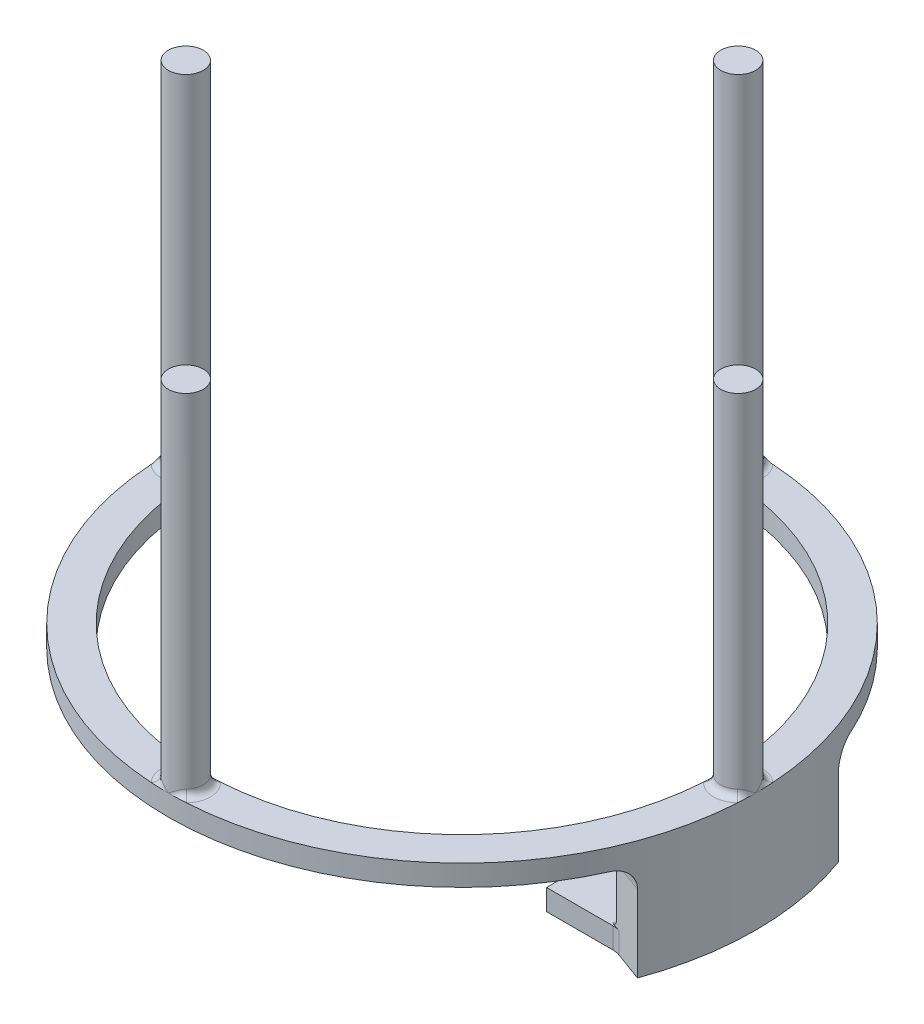
SolidWorks part; units mm, degrees
material "ABS"
ref_plane "前视基准面" through (0, 0, 0) normal (0, 0, 1) x (1, 0, 0)
ref_plane "上视基准面" through (0, 0, 0) normal (0, 1, 0) x (1, 0, 0)
ref_plane "右视基准面" through (0, 0, 0) normal (1, 0, 0) x (0, 0, -1)
other "Configuration Table"
sketch "草图1" plane through (0, 0, 0) normal (0, 1, 0) x (1, 0, 0)
  line L0 (-42, 0) -> (-37, 0)
  line L1 (0, 42) -> (0, 37)
  line L2 (0, 0) -> (0, 37) construction
  circle A0 centre (0, 0) radius 42 construction
  circle A1 centre (0, 0) radius 37 construction
  arc A2 (-37, 0) -> (0, 37) centre (0, 0) ccw
  arc A3 (-42, 0) -> (0, 42) centre (0, 0) ccw
  dimension "D1" = 84
  dimension "D2" = 74
extrude "凸台-拉伸1" add sketch "草图1" along normal blind 3
sketch "草图2" plane through (0, 3, 0) normal (0, 1, 0) x (1, 0, 0)
  line L0 (0, 42) -> (0, 37) construction
  line L1 (-37, 0) -> (-42, 0) construction
  line L2 (-39.5, 0) -> (0, 0) construction
  line L3 (0, 0) -> (0, 39.5) construction
  line L4 (0, 0) -> (39.5, 0) construction
  line L5 (0, 0) -> (0, -39.5) construction
  circle A0 centre (0, 39.5) radius 2.5
  circle A1 centre (-39.5, 0) radius 2.5
  circle A2 centre (39.5, 0) radius 2.5
  circle A3 centre (0, -39.5) radius 2.5
  point P15 (0, -44.3752)
extrude "凸台-拉伸2" add sketch "草图2" along normal blind 50 and the other way blind 3
sketch "草图3" plane through (0, 0, 0) normal (0, -1, 0) x (1, 0, 0)
  line L0 (0, 0) -> (82.8518, 0) construction
  line L1 (0, 0) -> (34.7686, 12.6547) construction
  line L2 (0, 0) -> (34.7686, -12.6547) construction
  line L3 (39.4671, 14.3648) -> (34.7686, 12.6547)
  line L4 (39.4671, -14.3648) -> (34.7686, -12.6547)
  arc A0 (0, -42) -> (-42, 0) centre (0, 0) ccw construction
  arc A1 (39.4671, -14.3648) -> (39.4671, 14.3648) centre (0, 0) ccw
  arc A2 (34.7686, -12.6547) -> (34.7686, 12.6547) centre (0, 0) ccw
  arc A3 (0, -37) -> (-37, 0) centre (0, 0) ccw construction
  dimension "D1" = 20
  dimension "D2" = 20
extrude "凸台-拉伸3" add sketch "草图3" along normal blind 14
sketch "草图4" plane through (0, -14, 0) normal (0, -1, 0) x (1, 0, 0)
  line L0 (34.7686, 12.6547) -> (24.75, 12.6547)
  line L1 (24.75, 12.6547) -> (24.75, -12.6547)
  line L2 (39.4671, 14.3648) -> (34.7686, 12.6547)
  line L3 (34.7686, -12.6547) -> (39.4671, -14.3648)
  line L4 (39.4671, 14.3648) -> (34.7686, 12.6547)
  line L5 (34.7686, -12.6547) -> (39.4671, -14.3648)
  line L6 (24.75, -12.6547) -> (34.7686, -12.6547)
  arc A2 (39.4671, -14.3648) -> (39.4671, 14.3648) centre (0, 0) ccw
  arc A3 (34.7686, -12.6547) -> (34.7686, 12.6547) centre (0, 0) ccw
  arc A4 (39.4671, -14.3648) -> (39.4671, 14.3648) centre (0, 0) ccw
  arc A5 (34.7686, -12.6547) -> (34.7686, 12.6547) centre (0, 0) ccw construction
  dimension "D2" = 24.75
  dimension "D1" = 0
extrude "凸台-拉伸4" add sketch "草图4" against normal blind 3
sketch "草图7" plane through (0, -11, 0) normal (0, 1, 0) x (1, 0, 0)
  circle A0 centre (32.25, 0) radius 1.45 construction
  circle A1 centre (32.25, 8) radius 1.45 construction
  circle A2 centre (32.25, 0) radius 1.45
  circle A3 centre (32.25, 8) radius 1.45
extrude "切除-拉伸1" cut sketch "草图7" against normal through all
fillet "圆角1" radius 3 4 edges at (37.1179, 0, -13.5098) (34.7686, -12.5, -12.6547) (34.7686, -12.5, 12.6547) (37.1179, 0, 13.5098)
fillet "圆角2" radius 1 7 edges at (-2.5, 3, 39.5) (2.5, 3, 39.5) (-39.5, 3, 2.5) (39.5, 3, 2.5) (39.5, 3, -2.5) (2.5, 3, -39.5) (37, -11, 0)
